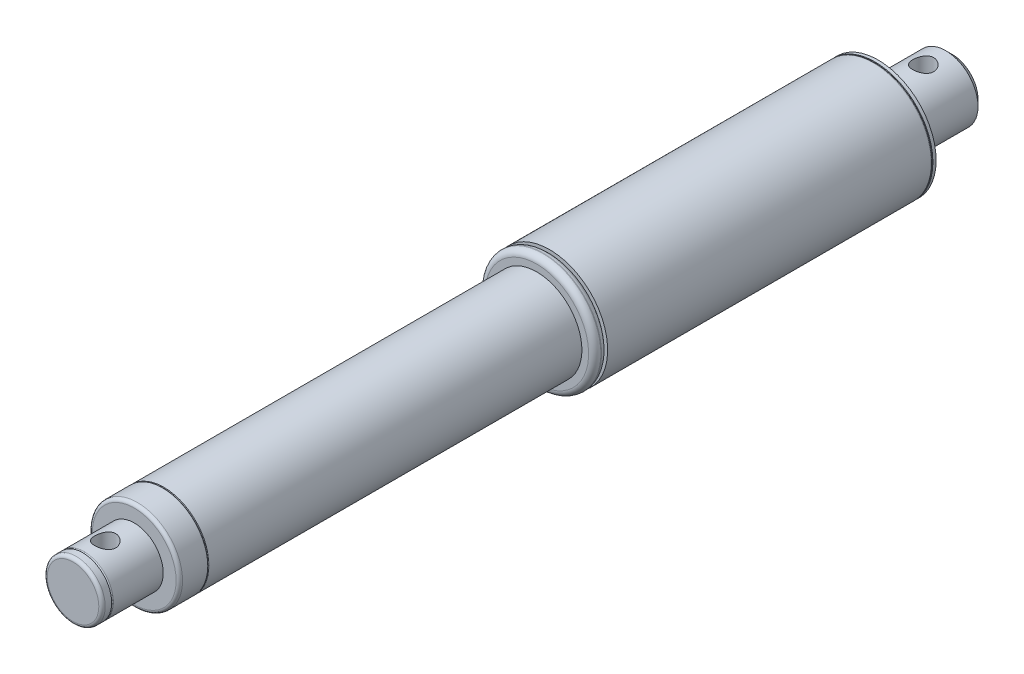
SolidWorks part; units mm, degrees
ref_plane "Спереди" through (0, 0, 0) normal (0, 0, 1) x (1, 0, 0)
ref_plane "Сверху" through (0, 0, 0) normal (0, 1, 0) x (1, 0, 0)
ref_plane "Справа" through (0, 0, 0) normal (1, 0, 0) x (0, 0, -1)
sketch "Эскиз1" plane through (0, 0, 0) normal (0, 0, 1) x (1, 0, 0)
  circle A0 centre (0, 0) radius 14
  dimension "D1" = 28
extrude "Бобышка-Вытянуть1" add sketch "Эскиз1" along normal blind 116
sketch "Эскиз2" plane through (0, 0, 0) normal (0, 0, -1) x (-1, 0, 0)
  circle A0 centre (0, 0) radius 18
  dimension "D1" = 36
extrude "Бобышка-Вытянуть2" add sketch "Эскиз2" along normal blind 4
fillet "Скругление1" radius 1.9 2 edges at (-18, 0, -4) (-18, 0, 0)
fillet "Скругление2" radius 0.2 1 edges at (14, 0, 116)
sketch "Эскиз3" plane through (0, 0, 116) normal (0, 0, 1) x (1, 0, 0)
  circle A0 centre (0, 0) radius 14
extrude "Бобышка-Вытянуть3" add sketch "Эскиз3" along normal blind 9
fillet "Скругление4" radius 0.2 1 edges at (14, 0, 116)
fillet "Скругление5" radius 1 1 edges at (14, 0, 125)
sketch "Эскиз4" plane through (0, 0, -4) normal (0, 0, -1) x (-1, 0, 0)
  circle A0 centre (0, 0) radius 18
  dimension "D1" = 36
extrude "Бобышка-Вытянуть4" add sketch "Эскиз4" along normal blind 101
sketch "Эскиз5" plane through (0, 0, 0) normal (1, 0, 0) x (0, 0, -1)
  line L0 (105, 0) -> (129, 0)
  line L1 (105, -18) -> (105, 18) construction
  line L2 (129, 0) -> (129, 8)
  line L3 (105, 18) -> (105, 0)
  line L4 (105, 18) -> (106, 18)
  line L5 (110, 10) -> (127, 10)
  line L6 (127, 10) -> (129, 8)
  arc A0 (106, 18) -> (110, 10) centre (86.9097, 3.4549) cw
  dimension "D1" = 5
  dimension "D7" = 24
  dimension "D2" = 1
  dimension "D3" = 10
  dimension "D4" = 8
  dimension "D5" = 2
  dimension "D6" = 24
  dimension "D8" = 18
fillet "Скругление6" radius 0.5 1 edges at (-18, 0, -105)
revolve "Повернуть1" add sketch "Эскиз5" angle 360 about L0
sketch "Эскиз6" plane through (0, 0, 125) normal (0, 0, 1) x (1, 0, 0)
  circle A0 centre (0, 0) radius 9
extrude "Бобышка-Вытянуть5" add sketch "Эскиз6" along normal blind 16
fillet "Скругление7" radius 0.5 1 edges at (9, 0, 141)
sketch "Эскиз7" plane through (0, 0, 141) normal (0, 0, 1) x (1, 0, 0)
  circle A0 centre (0, 0) radius 9
extrude "Бобышка-Вытянуть6" add sketch "Эскиз7" along normal blind 3
fillet "Скругление8" radius 1 1 edges at (9, 0, 144)
sketch "Эскиз8" plane through (0, 0, 0) normal (0, 1, 0) x (1, 0, 0)
  line L0 (8, 129) -> (-8, 129) construction
  line L1 (-8, -144) -> (8, -144) construction
  circle A0 centre (0, -134) radius 3.25
  circle A1 centre (0, 120) radius 3.25
  dimension "D1" = 9
  dimension "D2" = 6.5
  dimension "D4" = 6.5
  dimension "D3" = 10
extrude "Вырез-Вытянуть1" cut sketch "Эскиз8" against normal through all and the other way through all
